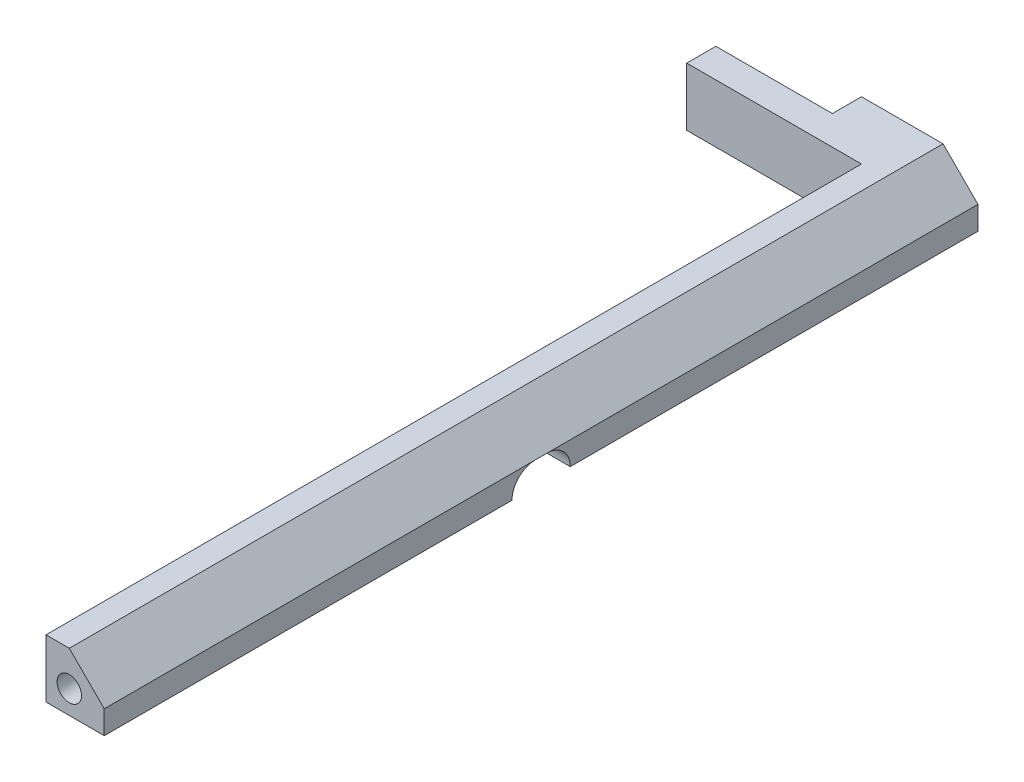
SolidWorks part; units mm, degrees
material "ABS"
ref_plane "Płaszczyzna przednia" through (0, 0, 0) normal (0, 0, 1) x (1, 0, 0)
ref_plane "Płaszczyzna górna" through (0, 0, 0) normal (0, 1, 0) x (1, 0, 0)
ref_plane "Płaszczyzna prawa" through (0, 0, 0) normal (1, 0, 0) x (0, 0, -1)
sketch "Szkic1" plane through (0, 0, 0) normal (0, 1, 0) x (1, 0, 0)
  line L0 (0, 0) -> (0, 150)
  line L1 (0, 150) -> (-20, 150)
  line L2 (-20, 150) -> (-20, 145)
  line L5 (-40, 140) -> (-10, 140)
  line L6 (-10, 140) -> (-10, 0)
  line L7 (-10, 0) -> (0, 0)
  line L8 (-40, 140) -> (-40, 145)
  line L9 (-40, 145) -> (-20, 145)
  dimension "D1" = 5
  dimension "D5" = 10
  dimension "D6" = 140
  dimension "D2" = 20
  dimension "D3" = 20
  dimension "D4" = 5
extrude "Dodanie-wyciągnięcie1" add sketch "Szkic1" along normal blind 10
sketch "Szkic2" plane through (0, 0, 0) normal (0, -1, 0) x (1, 0, 0)
  line L0 (0, 0) -> (0, -27) construction
  line L1 (0, 0) -> (0, -150) construction
  line L2 (0, -27) -> (-7.2, -27) construction
  line L3 (-7.2, -27) -> (-7.2, -123) construction
  circle A0 centre (-7.2, -123) radius 2.1
  circle A1 centre (-7.2, -27) radius 2.1
  dimension "D4" = 4.2
  dimension "D5" = 4.2
  dimension "D1" = 27
  dimension "D2" = 7.2
  dimension "D3" = 96
extrude "Wytnij-wyciągnięcie1" cut sketch "Szkic2" against normal blind 4
sketch "Szkic3" plane through (0, 0, 0) normal (0, 0, 1) x (1, 0, 0)
  line L0 (0, 0) -> (-6, 0) construction
  line L1 (-10, 0) -> (0, 0) construction
  line L2 (-6, 0) -> (-6, 4) construction
  circle A0 centre (-6, 4) radius 2.1
  dimension "D3" = 4.2
  dimension "D1" = 6
  dimension "D2" = 4
extrude "Wytnij-wyciągnięcie2" cut sketch "Szkic3" against normal blind 4
chamfer "Sfazowanie1" distance 6 angle 45 1 edges at (0, 10, -75)
sketch "Szkic4" plane through (0, 0, 0) normal (0, -1, 0) x (1, 0, 0)
  line L0 (0, 0) -> (0, -75) construction
  line L1 (0, 0) -> (0, -150) construction
  line L7 (0, -80) -> (0, -70)
  line L8 (0, -70) -> (-10, -70)
  line L9 (-10, -140) -> (-10, 0) construction
  line L10 (-10, -70) -> (-10, -80)
  line L11 (-10, -80) -> (0, -80)
  point P8 (0, -75)
  dimension "D1" = 75
  dimension "D2" = 10
extrude "Wytnij-wyciągnięcie3" cut sketch "Szkic4" against normal blind 4
fillet "Zaokrąglenie1" radius 4 2 edges at (-5, 4, -80) (-5, 4, -70)
equation "\"Lenght\"=140"
equation "\"Width\"=10"
equation "\"D5@Szkic1\"=\"Width\""
equation "\"D6@Szkic1\"=\"Lenght\""
equation "\"D4@Szkic1\"=\"Width\"/2"
equation "\"D1@Szkic1\"=\"Width\"/2"
equation "\"D1@Szkic2\"=(\"Lenght\"+\"Width\"-96)/2"
equation "\"InsertDiameter\"=4.2"
equation "\"D5@Szkic2\"=\"InsertDiameter\""
equation "\"D4@Szkic2\"=\"InsertDiameter\""
equation "\"D3@Szkic3\"=\"InsertDiameter\""
equation "\"D1@Szkic3\"=\"Width\"/2+1"
equation "\"D2@Szkic3\"=\"Width\"/2-1"
equation "\"D1@Szkic4\"=(\"Lenght\"+\"Width\")/2"
equation "\"D2@Szkic4\"=\"Width\""
